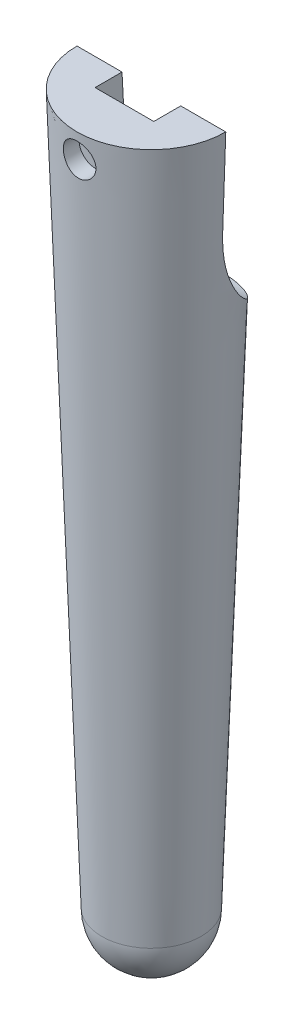
SolidWorks part; units mm, degrees
ref_plane "正面" through (0, 0, 0) normal (0, 0, 1) x (1, 0, 0)
ref_plane "平面" through (0, 0, 0) normal (0, 1, 0) x (1, 0, 0)
ref_plane "右側面" through (0, 0, 0) normal (1, 0, 0) x (0, 0, -1)
sketch "ｽｹｯﾁ1" plane through (0, 0, 0) normal (0, 1, 0) x (1, 0, 0)
  line L0 (0, -7) -> (0, 7) construction
  circle A0 centre (0, 0) radius 7
extrude "ﾎﾞｽ - 押し出し1" add sketch "ｽｹｯﾁ1" along normal blind 100 draft 2 draft outward yes
ref_plane "平面3" through (0, 100, 0) normal (0, 1, 0) x (1, 0, 0)
sketch "ｽｹｯﾁ14" plane through (0, 100, 0) normal (0, 1, 0) x (1, 0, 0)
  line L0 (0, 0) -> (0, -11.9927) construction
  line L1 (0, 0) -> (0, -3.8)
  circle A0 centre (0, 0) radius 11.9927
  dimension "D1" = 3.8
revolve "回転1" add sketch "ｽｹｯﾁ1<2>" angle 180 about L0 region at (-2.9709, 0, 0) reverse direction yes
sketch "ｽｹｯﾁ1<2>" plane through (0, 0, 0) normal (0, 1, 0) x (1, 0, 0) same geometry as "ｽｹｯﾁ1"
ref_plane "平面1" through (0, 0, 3.8) normal (0, 0, 1) x (1, 0, 0)
sketch "ｽｹｯﾁ6" plane through (0, 0, 3.8) normal (0, 0, 1) x (1, 0, 0)
  line L0 (-2.65, 94.3409) -> (-1.997, 82.3909)
  line L1 (2.65, 94.3409) -> (1.997, 82.3909)
  line L2 (0, 100) -> (0, 80.5) construction
  line L3 (0, 100) -> (-4.79, 100) construction
  line L4 (0, 100) -> (4.8238, 100) construction
  line L5 (0, 96.55) -> (3.45, 96.55) construction
  line L6 (3.45, 96.55) -> (3.6385, 100)
  line L7 (0, 96.55) -> (-3.45, 96.55) construction
  line L8 (-3.45, 96.55) -> (-3.6385, 100)
  line L9 (-3.6385, 100) -> (3.6385, 100)
  line L10 (-4.1666, 100.5) -> (4.1666, 100.5)
  line L11 (3.95, 96.5359) -> (4.1666, 100.5)
  line L12 (3.1405, 94.1543) -> (2.4963, 82.3636)
  line L13 (-3.1405, 94.1543) -> (-2.4963, 82.3636)
  line L14 (-3.95, 96.5359) -> (-4.1666, 100.5)
  arc A0 (2.65, 94.3409) -> (-2.65, 94.3409) centre (0, 96.55) ccw construction
  arc A1 (-1.997, 82.3909) -> (1.997, 82.3909) centre (0, 82.5) ccw construction
  arc A3 (-1.997, 82.3909) -> (1.997, 82.3909) centre (0, 82.5) ccw
  arc A5 (3.45, 96.55) -> (2.65, 94.3409) centre (0, 96.55) cw
  arc A6 (-3.45, 96.55) -> (-2.65, 94.3409) centre (0, 96.55) ccw
  arc A7 (3.95, 96.5359) -> (3.1405, 94.1543) centre (0, 96.55) cw
  arc A8 (-2.4963, 82.3636) -> (2.4963, 82.3636) centre (0, 82.5) ccw
  arc A9 (-3.95, 96.5359) -> (-3.1405, 94.1543) centre (0, 96.55) ccw
  dimension "D1" = 0.5
extrude "ｶｯﾄ - 押し出し5" cut sketch "ｽｹｯﾁ6" against normal through all contours L14 L10 L11 A7 L12 A8 L13 A9
ref_plane "平面2" through (0, 0, 7.9) normal (0, 0, -1) x (-1, 0, 0)
sketch "ｽｹｯﾁ10" plane through (0, 0, 7.9) normal (0, 0, -1) x (-1, 0, 0)
  circle A0 centre (0, 96.55) radius 1.05
extrude "ｶｯﾄ - 押し出し7" cut sketch "ｽｹｯﾁ10" along normal through all
sketch "ｽｹｯﾁ12" plane through (0, 0, 7.9) normal (0, 0, -1) x (-1, 0, 0)
  circle A0 centre (0, 96.55) radius 2.3
extrude "ｶｯﾄ - 押し出し8" cut sketch "ｽｹｯﾁ12" against normal through all
ref_plane "平面4" through (0, 100, 0) normal (0, 0, 1) x (1, 0, 0)
sketch "ｽｹｯﾁ15" plane through (0, 100, 0) normal (0, 0, 1) x (1, 0, 0)
  circle A0 centre (0, -3.45) radius 23.5
extrude "ｶｯﾄ - 押し出し9" cut sketch "ｽｹｯﾁ15" against normal through all
fillet "ﾌｨﾚｯﾄ1" radius 10 1 edges at (0, 73.05, 0)
